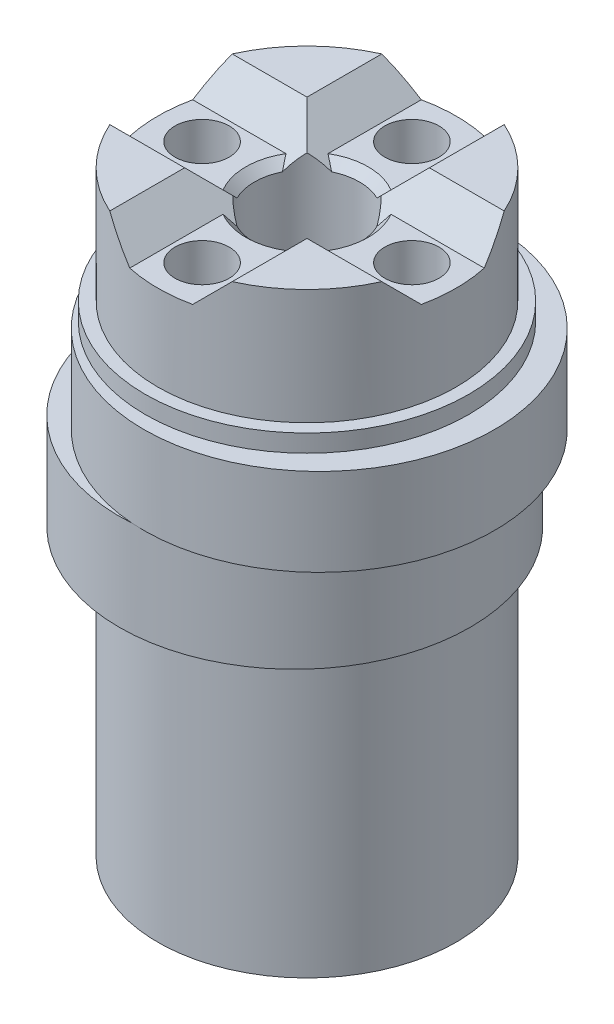
SolidWorks part; units mm, degrees
material "Like ABS"
ref_plane "Front Plane" through (0, 0, 0) normal (0, 0, 1) x (1, 0, 0)
ref_plane "Top Plane" through (0, 0, 0) normal (0, 1, 0) x (1, 0, 0)
ref_plane "Right Plane" through (0, 0, 0) normal (1, 0, 0) x (0, 0, -1)
sketch "Sketch1" plane through (0, 0, 0) normal (0, 1, 0) x (1, 0, 0)
  circle A0 centre (0, 0) radius 10.03
  dimension "D1" = 20.06
extrude "Boss-Extrude11" add sketch "Sketch1" along normal blind 5.5
sketch "Sketch20" plane through (0, 5.5, 0) normal (0, 1, 0) x (1, 0, 0)
  line L0 (0, 0) -> (1.4, 0) construction
  circle A0 centre (1.4, 0) radius 10.03
  dimension "D2" = 20.06
  dimension "D1" = 1.4
extrude "Boss-Extrude12" add sketch "Sketch20" along normal blind 5
sketch "Sketch21" plane through (0, 10.5, 0) normal (0, 1, 0) x (1, 0, 0)
  line L0 (0, 0) -> (0.7, 0) construction
  circle A0 centre (0.7, 0) radius 9.25
  dimension "D2" = 18.5
  dimension "D1" = 0.7
extrude "Boss-Extrude13" add sketch "Sketch21" along normal blind 1
sketch "Sketch22" plane through (0, 11.5, 0) normal (0, 1, 0) x (1, 0, 0)
  line L0 (0, 0) -> (0.7, 0) construction
  circle A0 centre (0.7, 0) radius 8.53
  dimension "D2" = 17.06
  dimension "D1" = 0.7
extrude "Boss-Extrude14" add sketch "Sketch22" along normal blind 6.6
sketch "Sketch30" plane through (0, 0, 0) normal (0, -1, 0) x (1, 0, 0)
  line L0 (0, 0) -> (0.7, 0) construction
  circle A1 centre (0.7, 0) radius 8.53
  dimension "D1" = 0.7
  dimension "D2" = 17.06
extrude "Boss-Extrude15" add sketch "Sketch30" along normal blind 16
sketch "Sketch31" plane through (0, 18.1, 0) normal (0, 1, 0) x (1, 0, 0)
  line L0 (0, 0) -> (0.7, 0) construction
  line L1 (0.7, 0) -> (6.7, 0) construction
  circle A0 centre (6.7, 0) radius 1.55
  dimension "D3" = 3.1
  dimension "D1" = 0.7
  dimension "D2" = 6
extrude "Cut-Extrude12" cut sketch "Sketch31" against normal up to surface (34.1 mm away) up to face at (0.7, -16, -8.53)
sketch "Sketch33" plane through (0, -16, 0) normal (0, -1, 0) x (1, 0, 0)
  line L0 (0, 0) -> (0.7, 0) construction
  circle A0 centre (0.7, 0) radius 2.1
  dimension "D2" = 4.2
  dimension "D1" = 0.7
extrude "Cut-Extrude14" cut sketch "Sketch33" against normal blind 5.8
sketch "Sketch36" plane through (0, 18.1, 0) normal (0, 1, 0) x (1, 0, 0)
  circle A0 centre (0.7, 0) radius 3
  dimension "D1" = 6
extrude "Cut-Extrude18" cut sketch "Sketch36" against normal up to surface (28.3 mm away) up to face at (0.7, -10.2, -2.1)
sketch "Sketch37" plane through (0, 18.1, 0) normal (0, 1, 0) x (1, 0, 0)
  line L0 (0.7, 2.1) -> (0.7, -2.1) construction
  line L1 (10.2, 3.5) -> (0.7, 3.5)
  line L2 (10.2, 3.5) -> (10.2, -3.5)
  line L3 (10.2, -3.5) -> (0.7, -3.5)
  line L4 (0.7, 3.5) -> (0.7, -3.5)
  circle A1 centre (0.7, 0) radius 2.1 construction
  point P12 (0.7, 0)
extrude "Cut-Extrude19" cut sketch "Sketch37" against normal blind 1.7
pattern_circular "CirPattern1" count 4 over 360 about axis through (0.7, 0, 0) along (0, 1, 0) of "Cut-Extrude19", "Cut-Extrude12"
chamfer "Chamfer1" distance 1.7 angle 45 20 edges at (8.4789, 17.25, 3.5) (8.4789, 17.25, -3.5) (6.3394, 16.4, -3.5) (6.3394, 16.4, 3.5) (-2.8, 17.25, -7.7789) (-2.8, 16.4, -5.6394) (-4.9394, 16.4, -3.5) (-7.0789, 17.25, -3.5) (-2.8, 17.25, -3.5) (-7.0789, 17.25, 3.5) (-4.9394, 16.4, 3.5) (-2.8, 16.4, 5.6394) (-2.8, 17.25, 7.7789) (-2.8, 17.25, 3.5) (4.2, 17.25, 7.7789) (4.2, 16.4, 5.6394) (4.2, 17.25, 3.5) (4.2, 16.4, -5.6394) (4.2, 17.25, -7.7789) (4.2, 17.25, -3.5)
chamfer "Chamfer2" distance 0.5 angle 45 4 edges at (3.7, 16.4, 0) (0.7, 16.4, 3) (-2.3, 16.4, 0) (0.7, 16.4, -3)
